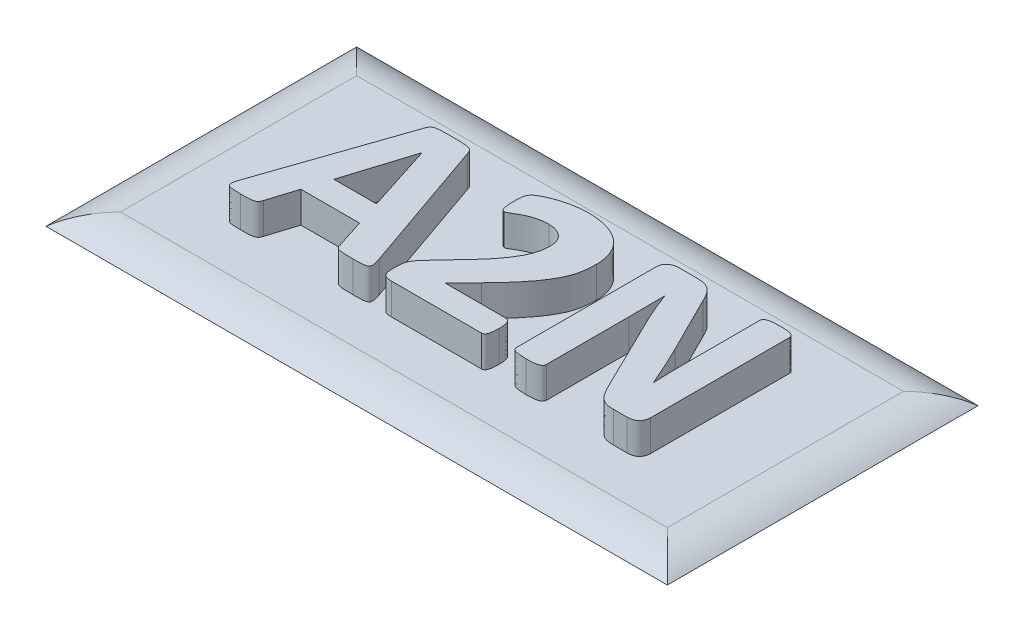
SolidWorks part; units mm, degrees
ref_plane "Front Plane" through (0, 0, 0) normal (0, 0, 1) x (1, 0, 0)
ref_plane "Top Plane" through (0, 0, 0) normal (0, 1, 0) x (1, 0, 0)
ref_plane "Right Plane" through (0, 0, 0) normal (1, 0, 0) x (0, 0, -1)
sketch "Sketch1" plane through (0, 0, 0) normal (0, 1, 0) x (1, 0, 0)
  line L1 (-50, 25) -> (50, 25)
  line L2 (-50, 25) -> (-50, -25)
  line L3 (-50, -25) -> (50, -25)
  line L4 (50, 25) -> (50, -25)
  line L5 (-50, 25) -> (50, -25) construction
  line L6 (-50, -25) -> (50, 25) construction
  point P0 (0, 0)
  dimension "D1" = 50
  dimension "D2" = 100
extrude "Boss-Extrude1" add sketch "Sketch1" along normal blind 2
fillet "Fillet1" radius 10 4 edges at (0, 2, 25) (-50, 2, 0) (0, 2, -25) (50, 2, 0)
sketch "Sketch2" plane through (0, 2, 0) normal (0, 1, 0) x (1, 0, 0)
  text T0 "<b>A2N</b>" font "Calibri" height 25
extrude "Boss-Extrude2" add sketch "Sketch2" along normal blind 5
